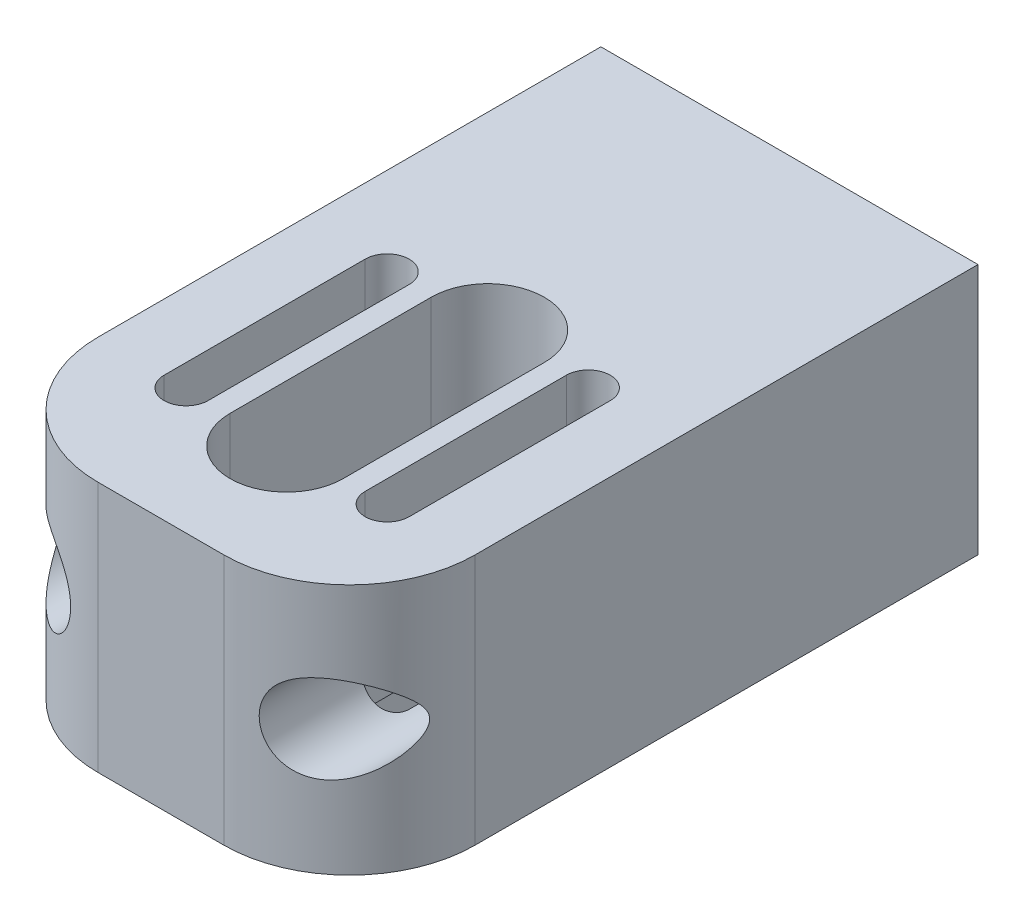
SolidWorks part; units mm, degrees
material "ABS"
ref_plane "Front Plane" through (0, 0, 0) normal (0, 0, 1) x (1, 0, 0)
ref_plane "Top Plane" through (0, 0, 0) normal (0, 1, 0) x (1, 0, 0)
ref_plane "Right Plane" through (0, 0, 0) normal (1, 0, 0) x (0, 0, -1)
sketch "Sketch1" plane through (0, 0, 0) normal (0, 0, 1) x (1, 0, 0)
  line L1 (-15.0008, -5.0578) -> (14.9992, -5.0578)
  line L2 (-15.0008, -5.0578) -> (-15.0008, 14.9422)
  line L3 (-15.0008, 14.9422) -> (14.9992, 14.9422)
  line L4 (14.9992, -5.0578) -> (14.9992, 14.9422)
  point P0 (0, 0)
  point P6 (0, 0)
  point P11 (0, 0)
  dimension "D1" = 20
  dimension "D3" = 30
extrude "Boss-Extrude1" add sketch "Sketch1" along normal blind 50
ref_plane "Plane1" through (-0.0008, 0, 0) normal (1, 0, 0) x (0, 0, -1)
sketch "Sketch3" plane through (0, 14.9422, 0) normal (0, 1, 0) x (1, 0, 0)
  line L1 (14.9992, -50) -> (-15.0008, -50) construction
  line L2 (-0.0009, -19.5) -> (-0.0009, -24) construction
  line L3 (-4.5008, -24) -> (-4.5002, -40)
  line L11 (-0.0007, -44.5) -> (-0.0006, -40) construction
  line L18 (4.4989, -40) -> (4.4989, -24)
  arc A6 (4.4989, -40) -> (-4.5002, -40) centre (-0.0006, -40) cw
  arc A7 (4.4989, -24) -> (-4.5008, -24) centre (-0.0009, -24) ccw
  dimension "D1" = 16
  dimension "D2" = 10
  dimension "D4" = 4.5
  dimension "D5" = 4.5
extrude "Cut-Extrude5" cut sketch "Sketch3" against normal through all
sketch "Sketch5" plane through (0, 14.9422, 0) normal (0, 1, 0) x (1, 0, 0)
  line L1 (-4.5002, -40) -> (-8.0008, -40) construction
  line L4 (-0.0008, -11) -> (-0.0008, 11) construction
  line L8 (-4.5008, -24) -> (-8.0008, -24) construction
  line L9 (-9.7511, -40) -> (-9.7511, -24)
  line L10 (-6.2505, -40) -> (-6.2505, -24)
  arc A8 (-6.2505, -40) -> (-9.7511, -40) centre (-8.0008, -40) cw
  arc A9 (-9.7511, -24) -> (-6.2505, -24) centre (-8.0008, -24) cw
  dimension "D1" = 8
extrude "Cut-Extrude2" cut sketch "Sketch5" against normal blind 20
sketch "Sketch6" plane through (0, -5.0578, 0) normal (0, -1, 0) x (1, 0, 0)
  line L0 (-9.7511, 40) -> (-6.2505, 24) construction
  line L1 (-6.2505, 40) -> (-9.7511, 24) construction
  line L8 (-11.0008, 43) -> (-5.0008, 43)
  line L9 (-11.0008, 43) -> (-11.0008, 21)
  line L10 (-11.0008, 21) -> (-5.0008, 21)
  line L11 (-5.0008, 43) -> (-5.0008, 21)
  line L12 (-11.0008, 43) -> (-5.0008, 21) construction
  line L13 (-11.0008, 21) -> (-5.0008, 43) construction
  point P9 (-8.0008, 32)
  dimension "D1" = 22
  dimension "D2" = 6
extrude "Cut-Extrude3" cut sketch "Sketch6" against normal blind 5
sketch "Sketch7" plane through (0, 0, 50) normal (0, 0, 1) x (1, 0, 0)
  line L0 (-15.0008, 4.9422) -> (14.9992, 4.9422) construction
  line L1 (-15.0008, 14.9422) -> (-15.0008, -5.0578) construction
  line L2 (14.9992, -5.0578) -> (14.9992, 14.9422) construction
  circle A0 centre (-11.0008, 4.9422) radius 1.75
  dimension "D1" = 3.5
  dimension "D3" = 4
extrude "Cut-Extrude4" cut sketch "Sketch7" against normal through all
hole_wizard "CBORE for M3 Hex Socket Head Cap Screw1" positions "Sketch9" profile "Sketch8" counterbore size "M3" standard "ISO" end condition through all
sketch "Sketch9" plane through (0, 0, 50) normal (0, 0, 1) x (1, 0, 0)
  point P0 (-11.0008, 4.9422)
sketch "Sketch8" plane through (-11.0008, 4.9422, 50) normal (1, 0, 0) x (0, -1, 0)
  line L0 (0, 0) -> (0, 50)
  line L1 (0, 50) -> (1.7, 50)
  line L3 (1.7, 50) -> (1.7, 38.4)
  line L4 (1.7, 38.4) -> (3.5, 38.4)
  line L5 (3.5, 38.4) -> (3.5, 0)
  line L7 (3.5, 0) -> (0, 0)
  line L11 (0, -6.35) -> (0, 107.95) construction
  dimension "Thru Hole Dia." = 3.4
  dimension "Thru Hole Depth" = 50
  dimension "C'Bore Dia." = 7
  dimension "C'Bore Depth" = 38.4
fillet "Fillet1" radius 10 2 edges at (-15.0008, 4.9422, 50) (14.9992, 4.9422, 50)
mirror "Mirror1" about plane through (-0.0008, 0, 0) normal (1, 0, 0) of "Cut-Extrude4", "Cut-Extrude2", "Cut-Extrude3", "CBORE for M3 Hex Socket Head Cap Screw1"
